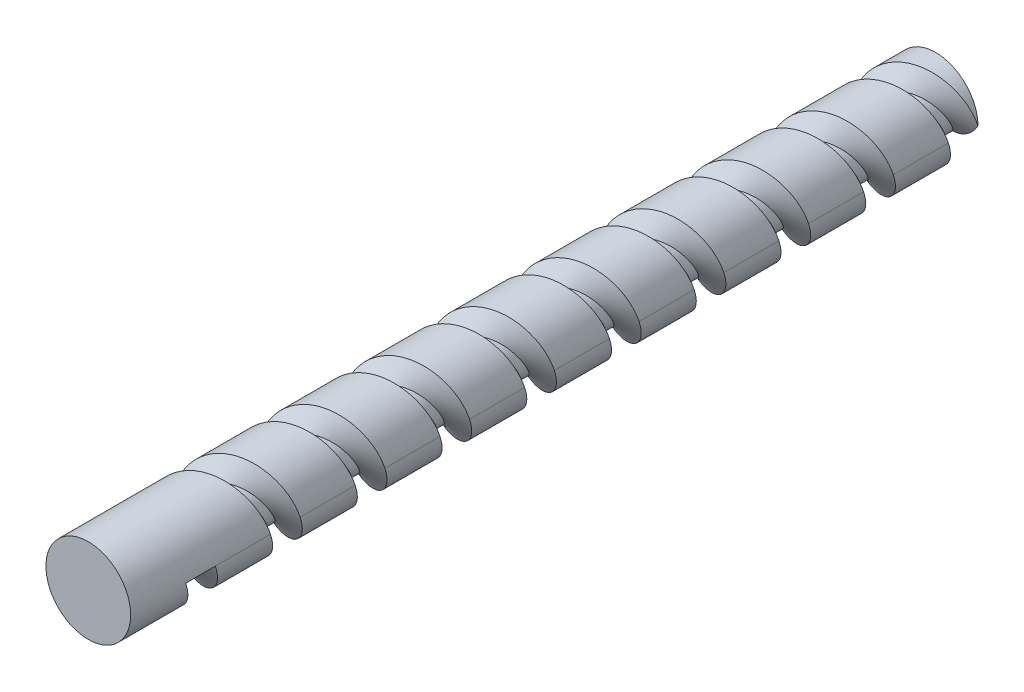
SolidWorks part; units mm, degrees
ref_plane "正面" through (0, 0, 0) normal (0, 0, 1) x (1, 0, 0)
ref_plane "平面" through (0, 0, 0) normal (0, 1, 0) x (1, 0, 0)
ref_plane "右側面" through (0, 0, 0) normal (1, 0, 0) x (0, 0, -1)
sketch "ｽｹｯﾁ1" plane through (0, 0, 0) normal (0, 0, 1) x (1, 0, 0)
  circle A0 centre (7.8709, 3.7524) radius 5
  dimension "D1" = 10
extrude "ﾎﾞｽ - 押し出し1" add sketch "ｽｹｯﾁ1" along normal blind 100
thread "ねじ山4" pitch 4 method cut profile "ねじ山の輪郭4" start angle 0, offset 10, length 100, pitch 10, diameter 10
ref_plane "平面4" through (12.8709, 3.7524, -10) normal (0, -1, 0) x (1, 0, 0)
sketch "ねじ山の輪郭4" plane through (12.8709, 3.7524, -10) normal (0, -1, 0) x (1, 0, 0)
  line L0 (0, 0) -> (0, 4) construction
  line L11 (0, 0) -> (0, 3.5)
  line L12 (0, 3.5) -> (-2.1651, 2.25)
  line L13 (-2.1651, 2.25) -> (-2.1651, 1.25)
  line L15 (-2.1651, 1.25) -> (0, 0)
  line L17 (-2.1651, 1.75) -> (0, 1.75) construction
  point P2 (0, 0)
  dimension "Pitch" = 4
  dimension "Profile_Angle" = 60
  dimension "Profile_Land" = 1
  dimension "Profile_Height" = 2.1651
